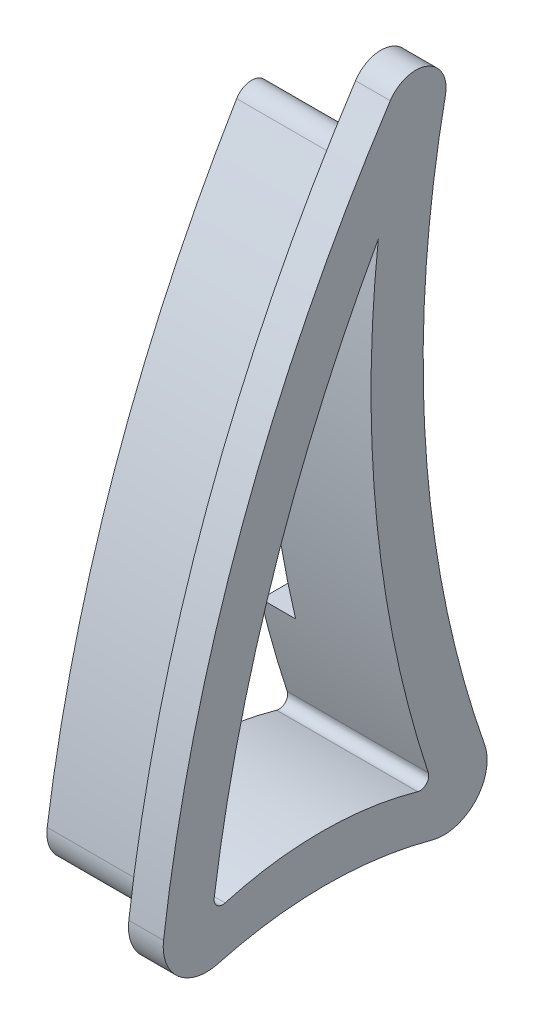
SolidWorks part; units mm, degrees
ref_plane "Front Plane" through (0, 0, 0) normal (0, 0, 1) x (1, 0, 0)
ref_plane "Top Plane" through (0, 0, 0) normal (0, 1, 0) x (1, 0, 0)
ref_plane "Right Plane" through (0, 0, 0) normal (1, 0, 0) x (0, 0, -1)
sketch "Sketch1" plane through (0, 0, 0) normal (0, 0, 1) x (1, 0, 0)
  line L0 (0, 0) -> (0, -27.8746) construction
  line L1 (-15.5575, 76.2) -> (15.5575, 76.2)
  line L2 (-15.5575, 76.2) -> (-15.5575, -76.2)
  line L3 (-15.5575, -76.2) -> (-7.8455, -76.2)
  line L4 (15.5575, 76.2) -> (15.5575, -76.2)
  line L5 (-15.5575, 76.2) -> (15.5575, -76.2) construction
  line L6 (-15.5575, -76.2) -> (15.5575, 76.2) construction
  line L7 (7.8455, -76.2) -> (9.525, -85.725)
  line L8 (-7.8455, -76.2) -> (-9.525, -85.725)
  line L9 (-9.525, -85.725) -> (9.525, -85.725)
  line L10 (7.8455, -76.2) -> (15.5575, -76.2)
  point P0 (0, 0)
  point P12 (0, -85.725)
  dimension "D1" = 31.115
  dimension "D2" = 152.4
  dimension "D3" = 20
  dimension "D4" = 19.05
  dimension "D5" = 9.525
extrude "Boss-Extrude1" add sketch "Sketch1" along normal blind 76.2
sketch "Sketch2" plane through (15.5575, 0, 0) normal (1, 0, 0) x (0, 0, -1)
  line L0 (-76.2, -76.2) -> (0, -76.2) construction
  line L1 (0, -85.725) -> (-6.985, -85.725)
  line L2 (0, -85.725) -> (0, -76.2)
  line L3 (0, -76.2) -> (-6.985, -76.2)
  line L4 (-6.985, -85.725) -> (-6.985, -76.2)
  dimension "D1" = 6.985
extrude "Cut-Extrude1" cut sketch "Sketch2" against normal through all
sketch "Sketch3" plane through (15.5575, 0, 0) normal (1, 0, 0) x (0, 0, -1)
  line L14 (-76.2, 76.2) -> (0, 76.2) construction
  line L15 (-76.2, -76.2) -> (-76.2, 76.2) construction
  line L16 (-76.2, -85.725) -> (-76.2, -76.2) construction
  line L17 (0, -76.2) -> (0, 76.2) construction
  line L18 (-76.2, -85.725) -> (-76.2, -76.2)
  line L19 (-76.2, -76.2) -> (-76.2, 76.2)
  line L20 (-76.2, 76.2) -> (-6.5418, 76.2)
  line L21 (0, -76.2) -> (0, 67.7594)
  arc A4 (-6.5418, 76.2) -> (-76.2, -85.725) centre (146.8317, -85.725) ccw
  arc A5 (0, 67.7594) -> (0, -76.2) centre (133.1876, -4.2203) ccw
  point P3 (0, 67.7594)
extrude "Cut-Extrude2" cut sketch "Sketch3" against normal through all
sketch "Sketch6" plane through (15.5575, 0, 0) normal (1, 0, 0) x (0, 0, -1)
  line L6 (-62.3225, -63.5) -> (-19.8242, -63.5)
  arc A2 (-28.9344, -61.8834) -> (-22.7163, -55.413) centre (-27.5427, -56.9978) ccw
  arc A3 (-55.008, -61.8834) -> (-61.4297, -56.2868) centre (-56.3997, -56.9978) cw
  arc A6 (-26.5466, 33.3523) -> (-19.8242, -63.5) centre (133.1876, -4.2203) ccw
  arc A7 (-26.5466, 33.3523) -> (-62.3225, -63.5) centre (146.8317, -85.725) ccw
  arc A11 (-26.5466, 33.3523) -> (-22.7163, -55.413) centre (133.1876, -4.2203) ccw
  arc A12 (-26.5466, 33.3523) -> (-61.4297, -56.2868) centre (146.8317, -85.725) ccw
  arc A13 (-55.008, -61.8834) -> (-28.9344, -61.8834) centre (-41.9712, -107.6502) cw
  point P7 (0, 0)
  dimension "D2" = 5.08
  dimension "D1" = 12.7
extrude "Cut-Extrude3" cut sketch "Sketch6" against normal through all
fillet "Fillet1" radius 2.54 1 edges at (0, 33.3523, 26.5466)
sketch "Sketch7" plane through (0, 0, 0) normal (1, 0, 0) x (0, 0, -1)
  line L0 (-30.6991, 4.0162) -> (-17.9818, 4.0162)
  line L2 (-26.2642, -42.9738) -> (-13.1619, -42.9738)
  arc A0 (-29.0387, 20.4641) -> (-22.7163, -55.413) centre (133.1876, -4.2203) ccw construction
  arc A1 (0, 67.7594) -> (0, -76.2) centre (133.1876, -4.2203) ccw construction
  arc A2 (-30.6991, 4.0162) -> (-26.2642, -42.9738) centre (133.1876, -4.2203) ccw
  arc A3 (-17.9818, 4.0162) -> (-13.1619, -42.9738) centre (133.1876, -4.2203) ccw
  dimension "D1" = 46.99
extrude "Cut-Extrude4" cut sketch "Sketch7" against normal mid plane 10.16
sketch "Sketch9" plane through (15.5575, 0, 0) normal (1, 0, 0) x (0, 0, -1)
  line L0 (-6.5418, 76.2) -> (0, 67.7594)
ref_plane "Plane2" through (15.5575, 76.2, 6.5418) normal (0, -0.7904, -0.6126) x (-1, 0, 0)
sketch "Sketch10" plane through (15.5575, 76.2, 6.5418) normal (0, -0.7904, -0.6126) x (-1, 0, 0)
  line L4 (15.5575, 5.1706) -> (15.5575, 19.0294) construction
  line L5 (0, 5.1706) -> (31.115, 5.1706) construction
  line L6 (0, 5.1706) -> (6.985, 5.1706)
  line L7 (6.985, 5.1706) -> (0, -3.6559)
  line L8 (0, 0) -> (0, -88.1882) construction
  line L9 (0, 5.1706) -> (0, -3.6559)
  line L10 (31.115, 5.1706) -> (31.115, -3.6559)
  line L11 (24.13, 5.1706) -> (31.115, -3.6559)
  line L12 (31.115, 5.1706) -> (24.13, 5.1706)
  dimension "D1" = 8.8265
  dimension "D2" = 6.985
extrude "Cut-Extrude6" cut sketch "Sketch10" against normal mid plane 30.226
fillet "Fillet2" radius 0.508 5 edges at (-15.5575, 5.0909, 56.873) (-14.1116, 74.9302, 7.8714) (0, 76.2, 6.5418) (15.5575, 5.0909, 56.873) (14.1116, 74.9302, 7.8714)
sketch "Sketch11" plane through (15.5575, 0, 0) normal (1, 0, 0) x (0, 0, -1)
  arc A0 (-61.4297, -56.2868) -> (-55.008, -61.8834) centre (-56.3997, -56.9978) ccw construction
  arc A1 (-28.9344, -61.8834) -> (-55.008, -61.8834) centre (-41.9712, -107.6502) ccw construction
  arc A2 (-28.9344, -61.8834) -> (-22.7163, -55.413) centre (-27.5427, -56.9978) ccw construction
  arc A3 (-29.0387, 20.4641) -> (-22.7163, -55.413) centre (133.1876, -4.2203) ccw construction
  arc A4 (-33.7303, 22.1489) -> (-61.4297, -56.2868) centre (146.8317, -85.725) ccw construction
  arc A5 (-29.0387, 20.4641) -> (-33.7303, 22.1489) centre (-31.5498, 20.8462) ccw construction
  arc A6 (-61.4297, -56.2868) -> (-55.008, -61.8834) centre (-56.3997, -56.9978) ccw
  arc A7 (-28.9344, -61.8834) -> (-55.008, -61.8834) centre (-41.9712, -107.6502) ccw
  arc A8 (-28.9344, -61.8834) -> (-22.7163, -55.413) centre (-27.5427, -56.9978) ccw
  arc A9 (-29.0387, 20.4641) -> (-22.7163, -55.413) centre (133.1876, -4.2203) ccw
  arc A10 (-33.7303, 22.1489) -> (-61.4297, -56.2868) centre (146.8317, -85.725) ccw
  arc A11 (-29.0387, 20.4641) -> (-33.7303, 22.1489) centre (-31.5498, 20.8462) ccw
  arc A12 (-57.6572, -56.82) -> (-56.0518, -58.2192) centre (-56.3997, -56.9978) ccw
  arc A13 (-27.8906, -58.2192) -> (-56.0518, -58.2192) centre (-41.9712, -107.6502) ccw
  arc A14 (-27.8906, -58.2192) -> (-26.3361, -56.6016) centre (-27.5427, -56.9978) ccw
  arc A15 (-33.6511, 14.6602) -> (-26.3361, -56.6016) centre (133.1876, -4.2203) ccw
  arc A16 (-33.6511, 14.6602) -> (-33.6511, 14.6602) centre (-33.6511, 14.6602) ccw
  arc A17 (-33.6511, 14.6602) -> (-57.6572, -56.82) centre (146.8317, -85.725) ccw
  dimension "D1" = 3.81
extrude "Boss-Extrude2" add sketch "Sketch11" against normal blind 15.5575 separate body
sketch "Sketch12" plane through (15.5575, 0, 0) normal (1, 0, 0) x (0, 0, -1)
  line L4 (-66.0068, -67.31) -> (-14.1573, -67.31)
  arc A0 (-23.8317, 27.9628) -> (-31.9051, 31.29) centre (-28.1862, 28.8553) ccw
  arc A1 (-57.0833, -65.4052) -> (-25.7615, -65.4052) centre (-41.4224, -122.6783) cw
  arc A2 (-27.8906, -58.2192) -> (-26.3361, -56.6016) centre (-27.5427, -56.9978) ccw construction
  arc A3 (-25.7615, -65.4052) -> (-18.0933, -57.1818) centre (-24.0866, -59.28) ccw
  arc A4 (-65.0563, -58.4699) -> (-57.0833, -65.4052) centre (-58.7582, -59.28) ccw
  arc A5 (-27.8906, -58.2192) -> (-56.0518, -58.2192) centre (-41.9712, -107.6502) ccw construction
  arc A6 (-17.255, 51.0774) -> (-66.0068, -67.31) centre (146.8317, -85.725) ccw
  arc A7 (-17.255, 51.0774) -> (-14.1573, -67.31) centre (133.1876, -4.2203) ccw
  arc A8 (-31.9051, 31.29) -> (-65.0563, -58.4699) centre (146.8317, -85.725) ccw
  arc A9 (-23.8317, 27.9628) -> (-18.0933, -57.1818) centre (133.1876, -4.2203) ccw
  arc A10 (-57.6572, -56.82) -> (-56.0518, -58.2192) centre (-56.3997, -56.9978) ccw construction
  arc A11 (-33.6511, 14.6602) -> (-57.6572, -56.82) centre (146.8317, -85.725) ccw construction
  arc A12 (-33.6511, 14.6602) -> (-26.3361, -56.6016) centre (133.1876, -4.2203) ccw construction
  arc A13 (-27.8906, -58.2192) -> (-26.3361, -56.6016) centre (-27.5427, -56.9978) ccw
  arc A14 (-27.8906, -58.2192) -> (-56.0518, -58.2192) centre (-41.9712, -107.6502) ccw
  arc A15 (-57.6572, -56.82) -> (-56.0518, -58.2192) centre (-56.3997, -56.9978) ccw
  arc A16 (-33.6511, 14.6602) -> (-57.6572, -56.82) centre (146.8317, -85.725) ccw
  arc A17 (-33.6511, 14.6602) -> (-26.3361, -56.6016) centre (133.1876, -4.2203) ccw
  point P11 (0, 0)
  dimension "D2" = 6.35
  dimension "D3" = 4.445
  dimension "D1" = 8.89
extrude "Boss-Extrude3" add sketch "Sketch12" along normal blind 5.08 separate body
sketch "Sketch13" plane through (0, 0, 0) normal (1, 0, 0) x (0, 0, -1)
  line L0 (-17.9818, 4.0162) -> (-34.5138, 4.0162)
  line L1 (-13.1619, -42.9738) -> (-30.1825, -42.9738)
  arc A0 (-33.6511, 14.6602) -> (-26.3361, -56.6016) centre (133.1876, -4.2203) ccw construction
  arc A1 (-1.8645, 64.1972) -> (0, -76.2) centre (133.1876, -4.2203) ccw construction
  arc A2 (-17.9818, 4.0162) -> (-13.1619, -42.9738) centre (133.1876, -4.2203) ccw
  arc A3 (-34.5138, 4.0162) -> (-30.1825, -42.9738) centre (133.1876, -4.2203) ccw
extrude "Cut-Extrude7" cut sketch "Sketch13" against normal mid plane 10.16
delete or keep bodies "Body-Delete/Keep 1" type delete bodies bodies 107
combine bodies "Combine1" operation type add bodies to combine 115 114
